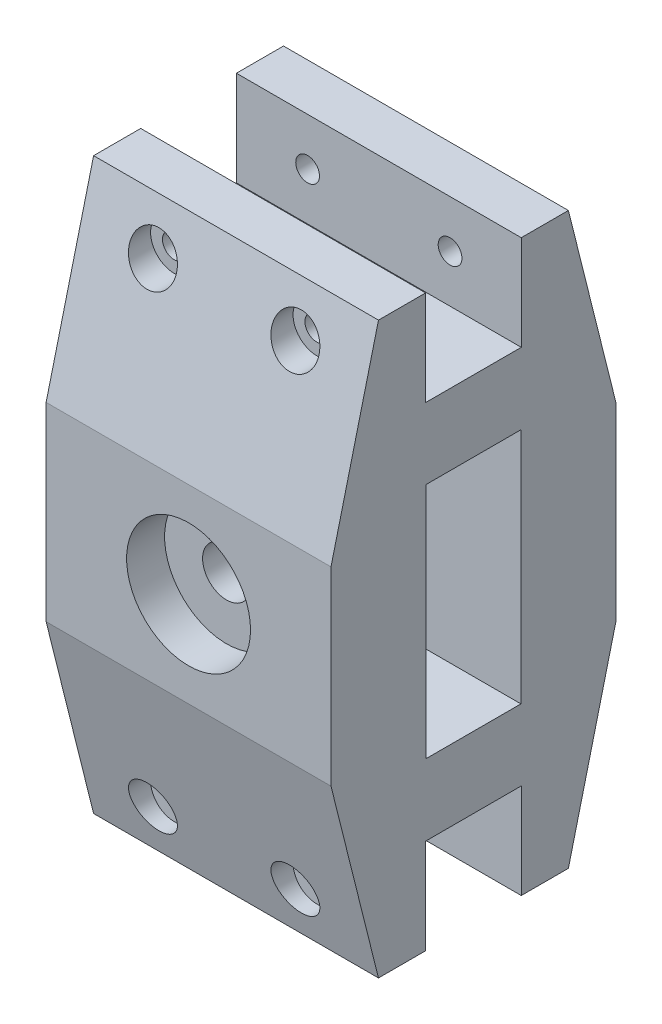
SolidWorks part; units mm, degrees
material "ABS"
ref_plane "Front Plane" through (0, 0, 0) normal (0, 0, 1) x (1, 0, 0)
ref_plane "Top Plane" through (0, 0, 0) normal (0, 1, 0) x (1, 0, 0)
ref_plane "Right Plane" through (0, 0, 0) normal (1, 0, 0) x (0, 0, -1)
sketch "Sketch2" plane through (0, 0, 0) normal (1, 0, 0) x (0, 0, -1)
  line L0 (30, 120) -> (30, 0) construction
  line L1 (0, 0) -> (60, 0)
  line L2 (0, 0) -> (0, 120)
  line L3 (0, 120) -> (60, 120)
  line L4 (60, 0) -> (60, 120)
  line L5 (30, 0) -> (60, 60) construction
  line L6 (60, 60) -> (0, 60) construction
  line L7 (0, 80) -> (10, 120)
  line L8 (60, 80) -> (50, 120)
  line L9 (60, 40) -> (50, 0)
  line L10 (0, 40) -> (10, 0)
  line L11 (19.925, 20) -> (40.075, 20)
  line L12 (19.925, 140) -> (40.075, 140)
  line L13 (19.925, 140) -> (19.925, 100)
  line L14 (19.925, 100) -> (40.075, 100)
  line L15 (40.075, 140) -> (40.075, 100)
  line L16 (19.925, 140) -> (40.075, 100) construction
  line L17 (19.925, 100) -> (40.075, 140) construction
  line L18 (40.075, -20) -> (40.075, 20)
  line L19 (19.925, -20) -> (40.075, -20)
  line L20 (19.925, -20) -> (19.925, 20)
  dimension "D1" = 60
  dimension "D2" = 120
  dimension "D3" = 20
  dimension "D4" = 20
  dimension "D5" = 20.15
  dimension "D6" = 20
extrude "Boss-Extrude1" add sketch "Sketch2" along normal blind 60 contours L2 L10 L1 L9 L4 L8 L3 L7 region at (0, 60, -30)
sketch "Sketch3" plane through (0, 0, 0) normal (0, 0, 1) x (1, 0, 0)
  line L0 (0, 60) -> (60, 60) construction
  line L1 (0, 40) -> (0, 80) construction
  line L2 (60, 40) -> (60, 80) construction
  line L3 (60, 60) -> (30, 120) construction
  line L4 (60, 120) -> (0, 120) construction
  line L5 (30, 120) -> (30, -5.0282) construction
  circle A0 centre (30, 60) radius 5.05
  dimension "D1" = 10.1
extrude "Cut-Extrude1" cut sketch "Sketch3" against normal blind 70
ref_plane "Plane1" through (0, 0, -30) normal (0, 0, 1) x (1, 0, 0)
sketch "Sketch4" plane through (0, 0, 0) normal (0, 0, 1) x (1, 0, 0)
  circle A0 centre (30, 60) radius 13.05
  dimension "D1" = 26.1
extrude "Cut-Extrude2" cut sketch "Sketch4" against normal blind 8
mirror "Mirror1" about plane through (0, 0, -30) normal (0, 0, 1) of "Cut-Extrude2"
sketch "Sketch5" plane through (0, 0, 0) normal (0, 0, 1) x (1, 0, 0)
  line L0 (30, 60) -> (89.4194, 60) construction
  line L1 (89.4194, 60) -> (-15.9572, 60) construction
  line L2 (-15.9572, 60) -> (30, 60) construction
  line L3 (30, 60) -> (30, 132.1461) construction
  line L4 (60, 120) -> (0, 120) construction
  circle A0 centre (45, 110) radius 2.5
  circle A1 centre (15, 110) radius 2.5
  circle A2 centre (45, 10) radius 2.5
  circle A3 centre (15, 10) radius 2.5
  dimension "D1" = 5
  dimension "D2" = 15
  dimension "D3" = 10
extrude "Cut-Extrude3" cut sketch "Sketch5" against normal through all
sketch "Sketch6" plane through (0, 0, 0) normal (0, 0, 1) x (1, 0, 0)
  line L0 (30, 120) -> (30, -1.9963) construction
  line L1 (60, 120) -> (0, 120) construction
  line L2 (30, -1.9963) -> (60, 60) construction
  line L3 (60, 40) -> (60, 80) construction
  line L4 (60, 60) -> (-4.5066, 60) construction
  circle A0 centre (45, 110) radius 500000
  circle A1 centre (45, 110) radius 5
  circle A2 centre (15, 110) radius 5
  circle A3 centre (15, 10) radius 5
  circle A4 centre (45, 10) radius 5
  dimension "D1" = 1000000
  dimension "D2" = 10
extrude "Cut-Extrude4" cut sketch "Sketch6" against normal blind 12 contours A2 | A1 | A3 | A4
mirror "Mirror2" about plane through (0, 0, -30) normal (0, 0, 1) of "Cut-Extrude4"
sketch "Sketch7" plane through (60, 0, 0) normal (1, 0, 0) x (0, 0, -1)
  line L0 (30, 20) -> (30, 100) construction
  line L1 (19.925, 20) -> (40.075, 20) construction
  line L2 (19.925, 100) -> (40.075, 100) construction
  line L3 (30, 100) -> (30, 60) construction
  line L4 (30, 60) -> (85.0304, 60) construction
  line L5 (0, 40) -> (0, 80) construction
  line L6 (20, 35) -> (40, 35)
  line L7 (20, 35) -> (20, 85)
  line L8 (20, 85) -> (40, 85)
  line L9 (40, 35) -> (40, 85)
  line L10 (20, 35) -> (40, 85) construction
  line L11 (20, 85) -> (40, 35) construction
  dimension "D1" = 15
  dimension "D2" = 20
extrude "Cut-Extrude5" cut sketch "Sketch7" against normal blind 81
